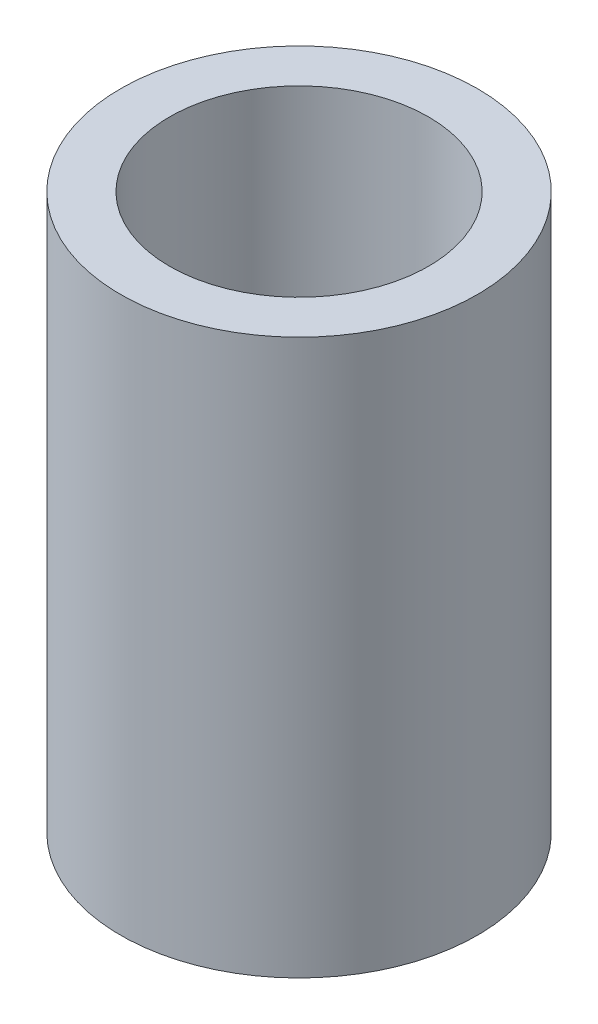
SolidWorks part; units mm, degrees
ref_plane "Front Plane" through (0, 0, 0) normal (0, 0, 1) x (1, 0, 0)
ref_plane "Top Plane" through (0, 0, 0) normal (0, 1, 0) x (1, 0, 0)
ref_plane "Right Plane" through (0, 0, 0) normal (1, 0, 0) x (0, 0, -1)
sketch "Sketch1" plane through (0, 0, 0) normal (0, 1, 0) x (1, 0, 0)
  circle A0 centre (0, 0) radius 6.75
extrude "Boss-Extrude1" add sketch "Sketch1" along normal blind 21
sketch "Sketch2" plane through (0, 21, 0) normal (0, 1, 0) x (1, 0, 0)
  circle A0 centre (0, 0) radius 4.9
extrude "Cut-Extrude1" cut sketch "Sketch2" against normal blind 10
sketch "Sketch3" plane through (0, 0, 0) normal (0, -1, 0) x (1, 0, 0)
  line L0 (-1.2975, -1.0984) -> (1.2975, -1.0984)
  line L1 (-1.15, -0.7984) -> (1.15, -0.7984)
  arc A0 (1.15, -0.7984) -> (-1.15, -0.7984) centre (0, 0) ccw
  arc A1 (1.2975, -1.0984) -> (-1.2975, -1.0984) centre (0, 0) ccw
  dimension "D1" = 2.3
  dimension "D2" = 1.4
  dimension "D3" = 0.3
extrude "Cut-Extrude2" cut sketch "Sketch3" against normal blind 8 contours A1 L0
